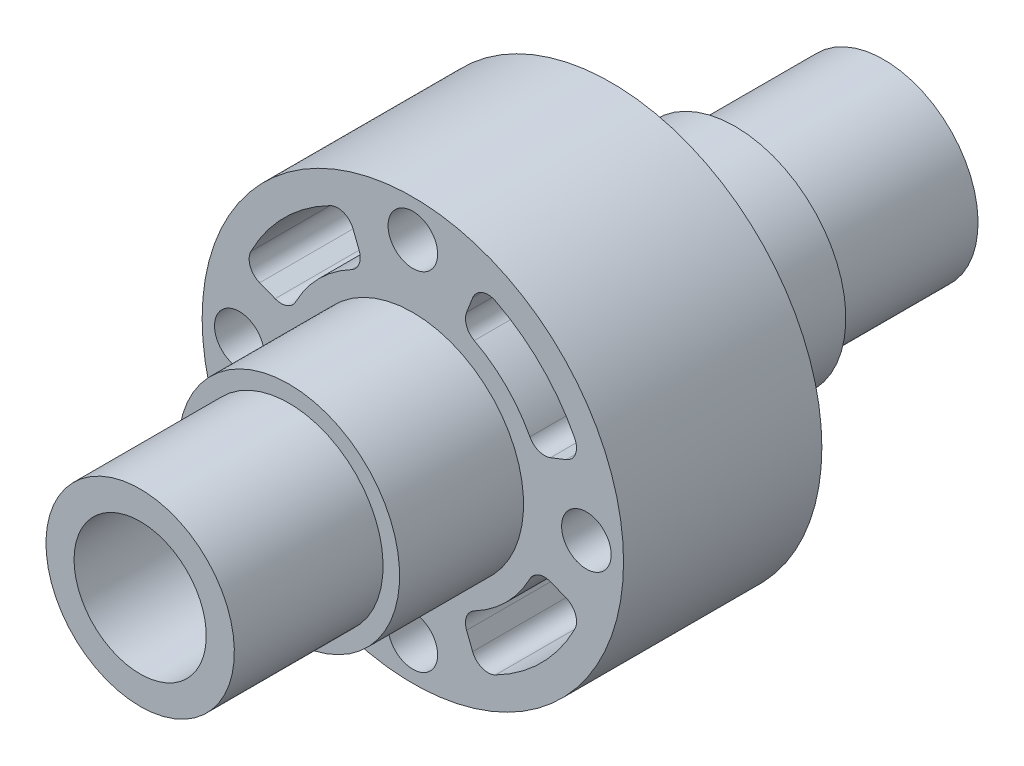
SolidWorks part; units mm, degrees
ref_plane "前视基准面" through (0, 0, 0) normal (0, 0, 1) x (1, 0, 0)
ref_plane "上视基准面" through (0, 0, 0) normal (0, 1, 0) x (1, 0, 0)
ref_plane "右视基准面" through (0, 0, 0) normal (1, 0, 0) x (0, 0, -1)
sketch "草图1" plane through (0, 0, 0) normal (1, 0, 0) x (0, 0, -1)
  line L0 (-21.2214, 0) -> (28.1258, 0) construction
  line L1 (-22.5, 0) -> (-22.5, 5.7)
  line L2 (-22.5, 5.7) -> (-13.5, 5.7)
  line L3 (-13.5, 5.7) -> (-13.5, 6.7) construction
  line L4 (-11.3555, 6.7) -> (-6, 6.7)
  line L5 (-6, 6.7) -> (-6, 14)
  line L6 (-6, 14) -> (6, 14)
  line L7 (0, 14) -> (0, 0) construction
  line L8 (6, 6.7) -> (6, 14)
  line L9 (11.3555, 6.7) -> (6, 6.7)
  line L10 (13.5, 5.7) -> (13.5, 6.7) construction
  line L11 (22.5, 5.7) -> (13.5, 5.7)
  line L12 (22.5, 0) -> (22.5, 5.7)
  line L13 (-22.5, 0) -> (22.5, 0)
  line L15 (-13.5, 6.7) -> (-11.3555, 6.7) construction
  line L17 (13.5, 6.7) -> (11.3555, 6.7) construction
  line L18 (11.3555, 6.7) -> (13.5, 6.7)
  line L19 (13.5, 6.7) -> (13.5, 5.7)
  line L20 (-11.3555, 6.7) -> (-13.5, 6.7)
  line L21 (-13.5, 6.7) -> (-13.5, 5.7)
  dimension "D1" = 5.7
  dimension "D2" = 12
  dimension "D3" = 14
  dimension "D4" = 9
  dimension "D5" = 7.5
  dimension "D6" = 6.7
  dimension "D7" = 45
revolve "旋转1" add sketch "草图1" angle 360 about L13
sketch "草图2" plane through (0, 0, 6) normal (0, 0, 1) x (1, 0, 0)
  line L0 (0, 0) -> (0, 10.5) construction
  circle A0 centre (0, 0) radius 10.5 construction
  circle A1 centre (0, 10.5) radius 1.5
  circle A2 centre (0, 0) radius 10.5 construction
  circle A3 centre (10.5, 0) radius 1.5
  circle A4 centre (0, 0) radius 10.5 construction
  circle A5 centre (0, -10.5) radius 1.5
  circle A6 centre (0, 0) radius 10.5 construction
  circle A7 centre (-10.5, 0) radius 1.5
  dimension "D1" = 21
  dimension "D2" = 3
  dimension "D3" = 4
extrude "切除-拉伸1" cut sketch "草图2" against normal through all
sketch "草图4" plane through (0, 0, -6) normal (0, 0, -1) x (-1, 0, 0)
  circle A0 centre (0, 0) radius 12.75
  circle A1 centre (0, 0) radius 14 construction
  circle A2 centre (0, 0) radius 14
  dimension "D1" = 25.5
extrude "切除-拉伸4" cut sketch "草图4" against normal through all
sketch "草图5" plane through (0, 0, -6) normal (0, 0, -1) x (-1, 0, 0)
  line L0 (-9.2687, 3.6181) -> (-8.332, 3.2525)
  line L1 (-3.6181, 9.2687) -> (-3.2525, 8.332)
  line L8 (3.6181, 9.2687) -> (3.2525, 8.332)
  line L9 (9.2687, 3.6181) -> (8.332, 3.2525)
  line L10 (9.2687, -3.6181) -> (8.332, -3.2525)
  line L11 (3.6181, -9.2687) -> (3.2525, -8.332)
  line L12 (-3.6181, -9.2687) -> (-3.2525, -8.332)
  line L13 (-9.2687, -3.6181) -> (-8.332, -3.2525)
  circle A2 centre (-10.5, 0) radius 1.5 construction
  circle A4 centre (0, 10.5) radius 1.5 construction
  arc A6 (-3.7191, 7.083) -> (-7.083, 3.7191) centre (0, 0) ccw
  arc A7 (-5.0046, 9.7956) -> (-9.7956, 5.0046) centre (0, 0) ccw
  arc A14 (-8.332, 3.2525) -> (-7.083, 3.7191) centre (-7.9683, 4.184) ccw
  arc A15 (-9.2687, 3.6181) -> (-9.7956, 5.0046) centre (-8.9051, 4.5497) cw
  arc A16 (-3.2525, 8.332) -> (-3.7191, 7.083) centre (-4.184, 7.9683) cw
  arc A17 (-3.6181, 9.2687) -> (-5.0046, 9.7956) centre (-4.5497, 8.9051) ccw
  arc A18 (3.6181, 9.2687) -> (5.0046, 9.7956) centre (4.5497, 8.9051) cw
  arc A19 (3.2525, 8.332) -> (3.7191, 7.083) centre (4.184, 7.9683) ccw
  arc A20 (7.083, 3.7191) -> (3.7191, 7.083) centre (0, 0) ccw
  arc A21 (8.332, 3.2525) -> (7.083, 3.7191) centre (7.9683, 4.184) cw
  arc A22 (9.2687, 3.6181) -> (9.7956, 5.0046) centre (8.9051, 4.5497) ccw
  arc A23 (9.7956, 5.0046) -> (5.0046, 9.7956) centre (0, 0) ccw
  arc A24 (9.2687, -3.6181) -> (9.7956, -5.0046) centre (8.9051, -4.5497) cw
  arc A25 (8.332, -3.2525) -> (7.083, -3.7191) centre (7.9683, -4.184) ccw
  arc A26 (3.7191, -7.083) -> (7.083, -3.7191) centre (0, 0) ccw
  arc A27 (3.2525, -8.332) -> (3.7191, -7.083) centre (4.184, -7.9683) cw
  arc A28 (3.6181, -9.2687) -> (5.0046, -9.7956) centre (4.5497, -8.9051) ccw
  arc A29 (5.0046, -9.7956) -> (9.7956, -5.0046) centre (0, 0) ccw
  arc A30 (-3.6181, -9.2687) -> (-5.0046, -9.7956) centre (-4.5497, -8.9051) cw
  arc A31 (-3.2525, -8.332) -> (-3.7191, -7.083) centre (-4.184, -7.9683) ccw
  arc A32 (-7.083, -3.7191) -> (-3.7191, -7.083) centre (0, 0) ccw
  arc A33 (-8.332, -3.2525) -> (-7.083, -3.7191) centre (-7.9683, -4.184) cw
  arc A34 (-9.2687, -3.6181) -> (-9.7956, -5.0046) centre (-8.9051, -4.5497) ccw
  arc A35 (-9.7956, -5.0046) -> (-5.0046, -9.7956) centre (0, 0) ccw
  point P23 (0, 0)
  point P25 (0, 0)
  point P27 (-10.247, 4)
  point P32 (-4, 10.247)
  point P44 (0, 0)
  point P57 (0, 0)
  point P63 (0, 0)
  dimension "D3" = 11
  dimension "D4" = 8
  dimension "D6" = 1
  dimension "D1" = 4
  dimension "D2" = 4
extrude "切除-拉伸5" cut sketch "草图5" against normal through all
sketch "草图6" plane through (0, 0, -22.5) normal (0, 0, -1) x (-1, 0, 0)
  circle A0 centre (0, 0) radius 4
  dimension "D1" = 8
extrude "切除-拉伸6" cut sketch "草图6" against normal through all
move or copy body "实体-移动/复制1" [suppressed] bodies to move or copy 113
